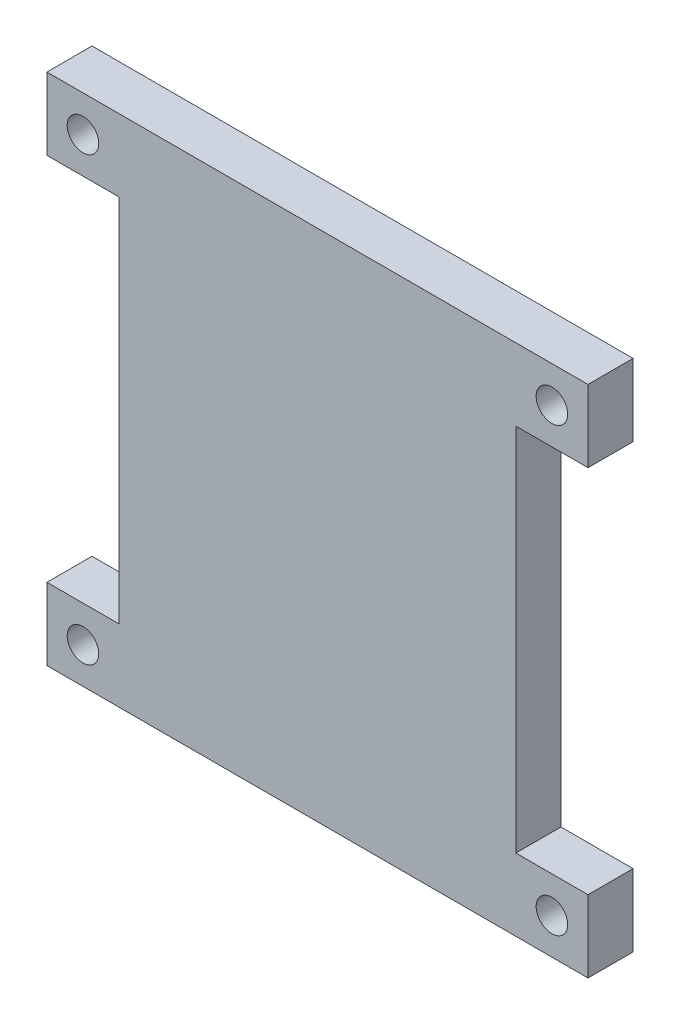
SolidWorks part; units mm, degrees
ref_plane "前基準面" through (0, 0, 0) normal (0, 0, 1) x (1, 0, 0)
ref_plane "上基準面" through (0, 0, 0) normal (0, 1, 0) x (1, 0, 0)
ref_plane "右基準面" through (0, 0, 0) normal (1, 0, 0) x (0, 0, -1)
sketch "草圖1" plane through (0, 0, 0) normal (0, 0, 1) x (1, 0, 0)
  line L1 (-22, 28.5) -> (22, 28.5)
  line L2 (-22, 28.5) -> (-22, -28.5)
  line L3 (-22, -28.5) -> (22, -28.5)
  line L4 (22, 28.5) -> (22, -28.5)
  line L5 (-22, 28.5) -> (22, -28.5) construction
  line L6 (-22, -28.5) -> (22, 28.5) construction
  line L7 (-30, 20.5) -> (-22, 20.5)
  line L8 (-30, 20.5) -> (-30, 28.5)
  line L9 (-30, 28.5) -> (-22, 28.5)
  line L10 (-22, 20.5) -> (-22, 28.5)
  line L11 (-30, 20.5) -> (-22, 28.5) construction
  line L12 (-30, 28.5) -> (-22, 20.5) construction
  line L13 (-30, -20.5) -> (-22, -20.5)
  line L14 (-30, -20.5) -> (-30, -28.5)
  line L15 (-30, -28.5) -> (-22, -28.5)
  line L16 (-22, -20.5) -> (-22, -28.5)
  line L17 (-30, -20.5) -> (-22, -28.5) construction
  line L18 (-30, -28.5) -> (-22, -20.5) construction
  line L19 (30, 20.5) -> (22, 20.5)
  line L20 (30, 20.5) -> (30, 28.5)
  line L21 (30, 28.5) -> (22, 28.5)
  line L22 (22, 20.5) -> (22, 28.5)
  line L23 (30, 20.5) -> (22, 28.5) construction
  line L24 (30, 28.5) -> (22, 20.5) construction
  line L25 (30, -20.5) -> (22, -20.5)
  line L26 (30, -20.5) -> (30, -28.5)
  line L27 (30, -28.5) -> (22, -28.5)
  line L28 (22, -20.5) -> (22, -28.5)
  line L29 (30, -20.5) -> (22, -28.5) construction
  line L30 (30, -28.5) -> (22, -20.5) construction
  circle A0 centre (-26, 24.5) radius 1.75
  circle A1 centre (26, 24.5) radius 1.75
  circle A2 centre (26, -24.5) radius 1.75
  circle A3 centre (-26, -24.5) radius 1.75
  point P0 (0, 0)
  point P6 (-26, 24.5)
  point P7 (-26, -24.5)
  point P11 (26, 24.5)
  point P15 (26, -24.5)
  dimension "D4" = 3.5
  dimension "D1" = 8
  dimension "D2" = 44
  dimension "D3" = 57
extrude "填料-伸長1" add sketch "草圖1" along normal blind 5 contours L9 L8 L7 L2 | L20 L21 L4 L19 | L27 L26 L25 L4 | L14 L15 L2 L13 | L4 L1 L2 L3 region at (0, 0, 0) region at (-22.1131, 24.5, 0) region at (26, 28.3869, 0) region at (-22.1131, -24.5, 0) region at (26, -20.6131, 0)
